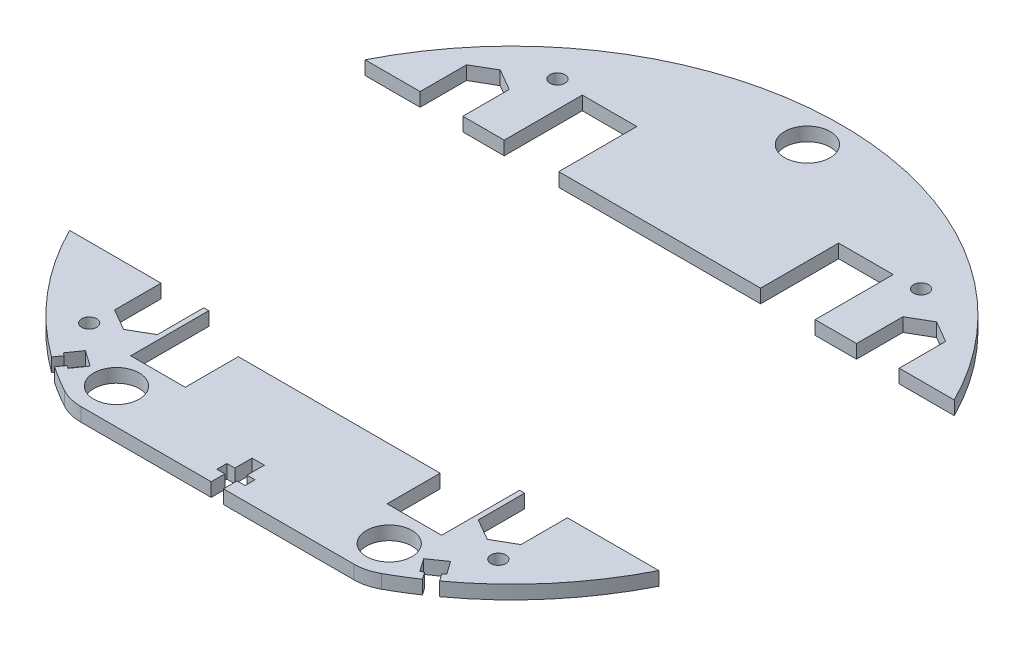
SolidWorks part; units mm, degrees
material "ABS"
ref_plane "Front Plane" through (0, 0, 0) normal (0, 0, 1) x (1, 0, 0)
ref_plane "Top Plane" through (0, 0, 0) normal (0, 1, 0) x (1, 0, 0)
ref_plane "Right Plane" through (0, 0, 0) normal (1, 0, 0) x (0, 0, -1)
sketch "Sketch1" plane through (0, 0, 0) normal (0, 1, 0) x (1, 0, 0)
  line L0 (-30.03, -64.8129) -> (30.03, -64.8129)
  line L1 (0, -85) -> (0, 0) construction
  line L2 (0, -85) -> (32.4891, -64.8129) construction
  arc A0 (34.8348, -63.5829) -> (-34.8348, -63.5829) centre (0, 0) ccw
  circle A1 centre (0, -85) radius 38.25 construction
  arc A2 (30.03, -64.8129) -> (34.8348, -63.5829) centre (30.03, -54.8129) ccw
  arc A3 (-30.03, -64.8129) -> (-34.8348, -63.5829) centre (-30.03, -54.8129) cw
  dimension "D1" = 145
  dimension "D2" = 76.5
  dimension "D4" = 10
  dimension "D3" = 85
extrude "Boss-Extrude1" add sketch "Sketch1" along normal blind 3
sketch "Sketch2" plane through (0, 3, 0) normal (0, 1, 0) x (1, 0, 0)
  line L0 (18, -36.1993) -> (-18, -36.1993) construction
  line L1 (-34.2, -49.6757) -> (-22.2, -49.6757)
  line L2 (-34.2, -49.6757) -> (-34.2, 49.6757)
  line L3 (-34.2, 49.6757) -> (-22.2, 49.6757)
  line L4 (-22.2, -49.6757) -> (-22.2, -38)
  line L6 (-22.2, -49.6757) -> (-22.2, -38)
  line L8 (19, 28.2007) -> (-19, 28.2007) construction
  line L9 (22.2, -38) -> (-22.2, -38)
  line L10 (-19, 32.5) -> (-22.2, 32.5) construction
  line L11 (-19, 32.5) -> (-22.2, 32.5)
  line L12 (19, 28.2007) -> (-19, 28.2007)
  line L15 (-19, 32.5) -> (-19, 28.2007)
  line L16 (-22.2, 32.5) -> (-22.2, 49.6757)
  line L17 (0, 0) -> (0, -64.8129) construction
  line L18 (-30.03, -64.8129) -> (30.03, -64.8129) construction
  line L19 (22.2, 32.5) -> (22.2, 49.6757)
  line L20 (19, 32.5) -> (19, 28.2007)
  line L23 (19, 32.5) -> (22.2, 32.5)
  line L25 (22.2, -49.6757) -> (22.2, -38)
  line L26 (22.2, -49.6757) -> (22.2, -38)
  line L27 (34.2, 49.6757) -> (22.2, 49.6757)
  line L28 (34.2, -49.6757) -> (34.2, 49.6757)
  line L29 (34.2, -49.6757) -> (22.2, -49.6757)
  dimension "D1" = 38
extrude "Cut-Extrude1" cut sketch "Sketch2" against normal through all contours L29 L28 L27 L19 L23 L20 L12 L15 L11 L16 L3 L2 L1 L4 L9 L25 region at (0, 3, 2.5352)
sketch "Sketch3" plane through (0, 3, 0) normal (0, 1, 0) x (1, 0, 0)
  line L0 (34.2, -32.5) -> (-34.2, -32.5)
  line L1 (-72.5, -32.5) -> (-34.2, -32.5)
  line L2 (-72.5, -32.5) -> (-72.5, 32.5)
  line L3 (-72.5, 32.5) -> (-34.2, 32.5)
  line L4 (72.5, -32.5) -> (72.5, 32.5)
  line L5 (-72.5, -32.5) -> (72.5, 32.5) construction
  line L6 (-72.5, 32.5) -> (72.5, -32.5) construction
  line L7 (-34.2, -49.6757) -> (-34.2, 49.6757) construction
  line L8 (34.2, 32.5) -> (-34.2, 32.5)
  line L9 (34.2, -49.6757) -> (34.2, 49.6757) construction
  line L10 (34.2, 32.5) -> (72.5, 32.5)
  line L11 (34.2, -32.5) -> (72.5, -32.5)
  arc A0 (34.8348, -63.5829) -> (-34.8348, -63.5829) centre (0, 0) ccw construction
  point P0 (0, 0)
  dimension "D1" = 65
extrude "Cut-Extrude2" cut sketch "Sketch3" against normal through all
sketch "Sketch4" plane through (0, 3, 0) normal (0, 1, 0) x (1, 0, 0)
  line L0 (0, 0) -> (0, -20.7985) construction
  circle A0 centre (30, -57) radius 5
  circle A4 centre (-30, -57) radius 5
  dimension "D3" = 10
  dimension "D1" = 57
  dimension "D2" = 30
extrude "Cut-Extrude3" cut sketch "Sketch4" against normal through all
sketch "Sketch5" plane through (0, 3, 0) normal (0, 1, 0) x (1, 0, 0)
  line L0 (-52.7, 37.2865) -> (-52.7, 32.5)
  line L2 (-34.2, 32.5) -> (-64.8074, 32.5) construction
  line L3 (-52.7, 32.5) -> (-43.3, 32.5)
  line L4 (-43.3, 32.5) -> (-43.3, 37.2865)
  line L6 (-44.7, -37.2865) -> (-44.7, -32.5)
  line L7 (-64.8074, -32.5) -> (-34.2, -32.5) construction
  line L8 (0, 0) -> (0, -64.8129) construction
  line L9 (-30.03, -64.8129) -> (30.03, -64.8129) construction
  line L16 (-35.3, -37.2865) -> (-35.3, -32.5)
  line L17 (-43.3, 42.7135) -> (-48, 45.4271)
  line L18 (-48, 45.4271) -> (-52.7, 42.7135)
  line L19 (-52.7, 42.7135) -> (-52.7, 37.2865)
  line L20 (-52.7, 37.2865) -> (-48, 34.5729) construction
  line L21 (-48, 34.5729) -> (-43.3, 37.2865) construction
  line L22 (-43.3, 37.2865) -> (-43.3, 42.7135)
  line L23 (-40, -34.5729) -> (-44.7, -37.2865) construction
  line L24 (-44.7, -37.2865) -> (-44.7, -42.7135)
  line L25 (-44.7, -42.7135) -> (-40, -45.4271)
  line L26 (-40, -45.4271) -> (-35.3, -42.7135)
  line L27 (-35.3, -42.7135) -> (-35.3, -37.2865)
  line L28 (-35.3, -37.2865) -> (-40, -34.5729) construction
  line L30 (-35.3, -32.5) -> (-44.7, -32.5)
  line L31 (35.3, -37.2865) -> (40, -34.5729) construction
  line L32 (40, -34.5729) -> (44.7, -37.2865) construction
  line L33 (48, 34.5729) -> (43.3, 37.2865) construction
  line L34 (52.7, 37.2865) -> (48, 34.5729) construction
  line L35 (35.3, -32.5) -> (44.7, -32.5)
  line L36 (35.3, -42.7135) -> (35.3, -37.2865)
  line L37 (40, -45.4271) -> (35.3, -42.7135)
  line L38 (44.7, -42.7135) -> (40, -45.4271)
  line L39 (44.7, -37.2865) -> (44.7, -42.7135)
  line L40 (43.3, 37.2865) -> (43.3, 42.7135)
  line L41 (52.7, 42.7135) -> (52.7, 37.2865)
  line L42 (48, 45.4271) -> (52.7, 42.7135)
  line L43 (43.3, 42.7135) -> (48, 45.4271)
  line L44 (35.3, -37.2865) -> (35.3, -32.5)
  line L45 (44.7, -37.2865) -> (44.7, -32.5)
  line L46 (43.3, 32.5) -> (43.3, 37.2865)
  line L47 (52.7, 32.5) -> (43.3, 32.5)
  line L48 (52.7, 37.2865) -> (52.7, 32.5)
  circle A2 centre (-48, 40) radius 4.7 construction
  circle A3 centre (-40, -40) radius 4.7 construction
  circle A4 centre (40, -40) radius 4.7 construction
  circle A5 centre (48, 40) radius 4.7 construction
  dimension "D1" = 9.4
  dimension "D2" = 48
  dimension "D3" = 40
  dimension "D4" = 40
  dimension "D5" = 40
  dimension "D6" = 9.4
extrude "Cut-Extrude4" cut sketch "Sketch5" against normal through all
sketch "Sketch7" plane through (0, 3, 0) normal (0, 1, 0) x (1, 0, 0)
  line L0 (0, 0) -> (0, 65) construction
  circle A0 centre (0, 65) radius 5
  dimension "D1" = 10
  dimension "D2" = 65
extrude "Cut-Extrude6" cut sketch "Sketch7" against normal through all
sketch "Sketch8" plane through (0, 3, 0) normal (0, 1, 0) x (1, 0, 0)
  line L0 (-1.35, -64.8129) -> (-1.35, -61.8129)
  line L1 (-30.03, -64.8129) -> (30.03, -64.8129) construction
  line L2 (-1.35, -61.8129) -> (-3.1, -61.8129)
  line L3 (-3.1, -61.8129) -> (-3.1, -59.6129)
  line L4 (-3.1, -59.6129) -> (-1.35, -59.6129)
  line L5 (-1.35, -59.6129) -> (-1.35, -55.8129)
  line L6 (-1.35, -55.8129) -> (1.35, -55.8129)
  line L7 (1.35, -55.8129) -> (1.35, -59.6129)
  line L8 (1.35, -59.6129) -> (3.1, -59.6129)
  line L9 (3.1, -59.6129) -> (3.1, -61.8129)
  line L10 (3.1, -61.8129) -> (1.35, -61.8129)
  line L11 (1.35, -61.8129) -> (1.35, -64.8129)
  line L12 (-1.35, -64.8129) -> (1.35, -64.8129)
  line L13 (-30.03, -64.8129) -> (30.03, -64.8129) construction
  point P18 (0, -64.8129)
  point P19 (0, -64.8129)
  dimension "D1" = 2.7
  dimension "D2" = 2.2
  dimension "D3" = 6.2
  dimension "D5" = 9
extrude "Cut-Extrude7" cut sketch "Sketch8" against normal through all
sketch "Sketch9" plane through (0, 3, 0) normal (0, 1, 0) x (1, 0, 0)
  line L0 (0, 0) -> (0, -27.4582) construction
  circle A0 centre (45, -48) radius 1.65
  circle A1 centre (-45, -48) radius 1.65
  circle A2 centre (40, 50) radius 1.65
  circle A3 centre (-40, 50) radius 1.65
  dimension "D3" = 3.3
  dimension "D1" = 45
  dimension "D2" = 48
  dimension "D4" = 40
  dimension "D5" = 50
extrude "Cut-Extrude8" cut sketch "Sketch9" against normal through all
sketch "Sketch10" plane through (0, 3, 0) normal (0, 1, 0) x (1, 0, 0)
  line L0 (0, 0) -> (0, -38) construction
  line L1 (-22.2, -38) -> (22.2, -38) construction
  line L2 (0, 0) -> (41.5843, -59.3885) construction
  line L3 (36.6889, -56.102) -> (40.1703, -53.6643)
  line L4 (36.6889, -56.102) -> (38.6964, -58.9691)
  line L5 (40.1703, -53.6643) -> (42.1778, -56.5314)
  line L6 (38.6964, -58.9691) -> (39.3313, -58.5245)
  line L7 (39.3313, -58.5245) -> (40.4784, -60.1629)
  line L8 (40.4784, -60.1629) -> (42.6901, -58.6142)
  line L9 (42.6901, -58.6142) -> (41.543, -56.9759)
  line L10 (41.543, -56.9759) -> (42.1778, -56.5314)
  line L11 (-41.543, -56.9759) -> (-42.1778, -56.5314)
  line L12 (-42.6901, -58.6142) -> (-41.543, -56.9759)
  line L13 (-40.4784, -60.1629) -> (-42.6901, -58.6142)
  line L14 (-39.3313, -58.5245) -> (-40.4784, -60.1629)
  line L15 (-38.6964, -58.9691) -> (-39.3313, -58.5245)
  line L16 (-40.1703, -53.6643) -> (-42.1778, -56.5314)
  line L17 (-36.6889, -56.102) -> (-38.6964, -58.9691)
  line L18 (-36.6889, -56.102) -> (-40.1703, -53.6643)
  arc A0 (34.8348, -63.5829) -> (64.8074, -32.5) centre (0, 0) ccw construction
  point P5 (38.4296, -54.8832)
  point P18 (41.5843, -59.3885)
  dimension "D1" = 35
  dimension "D2" = 4.25
  dimension "D3" = 3.5
  dimension "D4" = 2.7
extrude "Cut-Extrude9" cut sketch "Sketch10" against normal through all
equation "\"smallPulleyTeeth\"= 30"
equation "\"largePulleyTeeth\"= 30"
equation "\"eighthThick\"= 3.0mm"
equation "\"sixteenthThick\" = 1.7mm"
equation "\"quarterThick\"=6.0mm"
equation "\"OD\" = 145mm"
equation "\"puckAngle\" = 60.5deg"
equation "\"puckDiam\" = 76.5mm"
equation "\"axlePress\" = 5.9mm"
equation "\"press\" = 0.2mm"
equation "\"wheelClear\" = 0.3mm"
equation "\"10-32clear\" = 4.8mm"
equation "\"6-32clear\" = 3.3mm"
equation "\"8-32clear\" = 4.0mm"
equation "\"4-40clear\" = 3.0mm"
equation "\"wheelHeight\" = 22mm"
equation "\"wheelWell\" = 65mm"
equation "\"D1@Sketch1\"=\"OD\""
equation "\"D1@Boss-Extrude1\"=\"eighthThick\""
equation "\"D2@Sketch1\"=\"puckDiam\""
equation "\"D1@Sketch3\"=\"wheelWell\""
equation "\"puckDist\" = 85mm"
equation "\"scoopFillet\" = 5mm"
equation "\"10-32tap\" = 4.45mm"
equation "\"ledSmall\" = 3.1mm"
equation "\"ledLarge\" = 4.2mm"
equation "\"ledLength\" = 4.2mm"
equation "\"D3@Sketch1\"=\"puckDist\""
equation "\"4-40close\" = 2.7mm"
equation "\"4-40nutThick\" = 2.2mm"
equation "\"4-40nutWidth\" = 6.2mm"
equation "\"D1@Sketch8\"=\"4-40close\""
equation "\"D3@Sketch8\"=\"4-40nutWidth\""
equation "\"D3@Sketch9\"=\"6-32clear\""
equation "\"4-40insertHeight\" = 3.5mm"
equation "\"4-40insert\" = 4.25mm"
equation "\"D2@Sketch10\"=\"4-40insert\""
equation "\"D3@Sketch10\"=\"4-40insertHeight\""
equation "\"D4@Sketch10\"=\"4-40close\""
